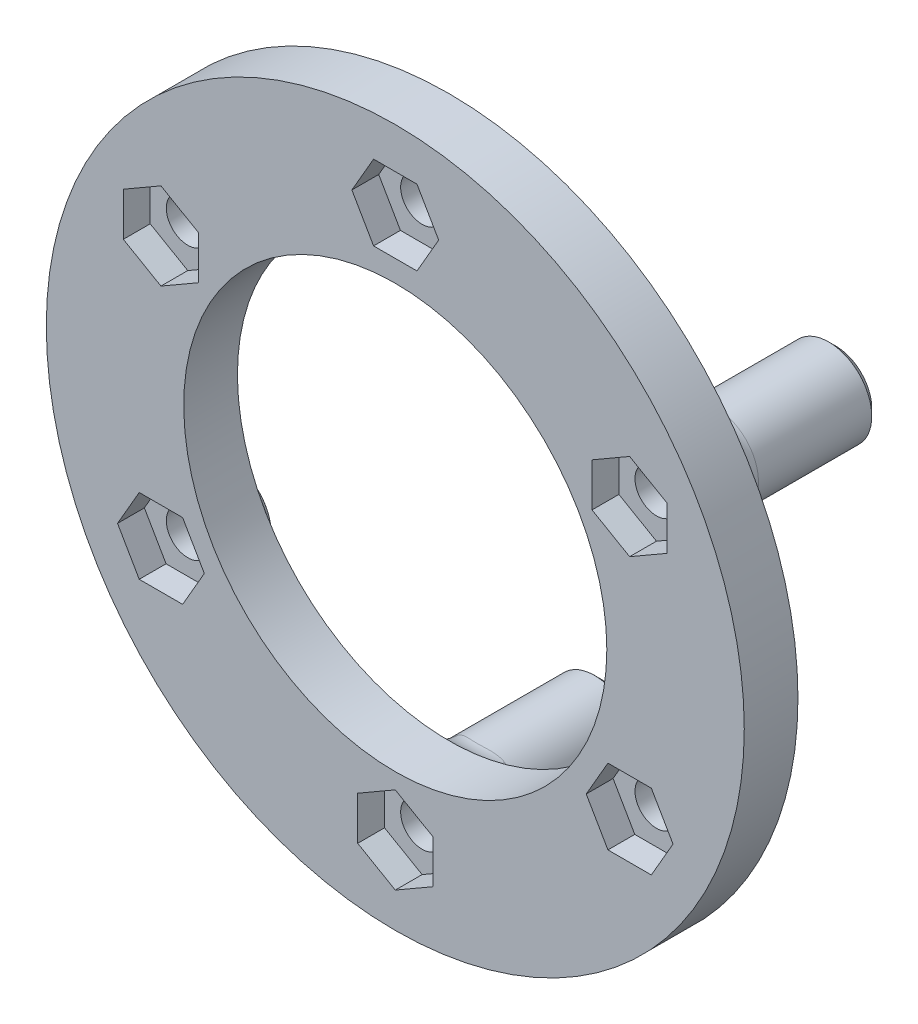
SolidWorks part; units mm, degrees
material "ABS"
ref_plane "Front Plane" through (0, 0, 0) normal (0, 0, 1) x (1, 0, 0)
ref_plane "Top Plane" through (0, 0, 0) normal (0, 1, 0) x (1, 0, 0)
ref_plane "Right Plane" through (0, 0, 0) normal (1, 0, 0) x (0, 0, -1)
sketch "Sketch2" plane through (0, 0, 0) normal (0, 0, 1) x (1, 0, 0)
  line L0 (0, 25.2) -> (0, 0) construction
  line L1 (0, 0) -> (24.6817, 14.25) construction
  circle A0 centre (0, 0) radius 32.5
  circle A1 centre (0, 0) radius 19.7
  circle A2 centre (0, 0) radius 25.2 construction
  circle A3 centre (0, 25.2) radius 2
  circle A4 centre (0, 0) radius 28.5 construction
  circle A5 centre (21.8238, 12.6) radius 2
  circle A11 centre (0, 0) radius 5.4 construction
  circle A14 centre (0, 25.2) radius 4 construction
  circle A15 centre (0, 0) radius 21.2 construction
  circle A20 centre (21.8238, -12.6) radius 2
  circle A21 centre (0, -25.2) radius 2
  circle A22 centre (-21.8238, -12.6) radius 2
  circle A23 centre (-21.8238, 12.6) radius 2
  point P17 (0, 0)
  point P24 (0, 0)
  dimension "D1" = 65
  dimension "D2" = 50.4
  dimension "D4" = 4
  dimension "D3" = 10.8
  dimension "D10" = 8
  dimension "D5" = 4
  dimension "D9" = 1.5
  dimension "D11" = 60
  dimension "D6" = 6
extrude "Boss-Extrude1" add sketch "Sketch2" along normal blind 5
sketch "Sketch3" plane through (0, 0, 5) normal (0, 0, 1) x (1, 0, 0)
  line L0 (0, 25.2) -> (0, 0) construction
  line L13 (-4.0415, 25.2) -> (-2.0207, 21.7)
  line L14 (-2.0207, 21.7) -> (2.0207, 21.7)
  line L15 (2.0207, 21.7) -> (4.0415, 25.2)
  line L16 (4.0415, 25.2) -> (2.0207, 28.7)
  line L17 (2.0207, 28.7) -> (-2.0207, 28.7)
  line L18 (-2.0207, 28.7) -> (-4.0415, 25.2)
  line L20 (21.8238, 8.5585) -> (25.3238, 10.5793)
  line L21 (25.3238, 10.5793) -> (25.3238, 14.6207)
  line L22 (25.3238, 14.6207) -> (21.8238, 16.6415)
  line L23 (21.8238, 16.6415) -> (18.3238, 14.6207)
  line L24 (18.3238, 14.6207) -> (18.3238, 10.5793)
  line L25 (18.3238, 10.5793) -> (21.8238, 8.5585)
  circle A0 centre (0, 25.2) radius 3.5 construction
  circle A1 centre (21.8238, 12.6) radius 3.5 construction
  dimension "D1" = 7
  dimension "D2" = 7
extrude "Cut-Extrude1" cut sketch "Sketch3" against normal blind 2.5
pattern_circular "CirPattern1" count 3 over 360 about axis through (0, 0, 0) along (0, 0, 1) of "Cut-Extrude1"
sketch "Sketch4" plane through (0, 0, 0) normal (0, 0, -1) x (-1, 0, 0)
  circle A0 centre (0, 25.2) radius 3
  circle A1 centre (0, 25.2) radius 4
  dimension "D1" = 6
extrude "Boss-Extrude2" add sketch "Sketch4" along normal blind 1.5
fillet "Fillet1" radius 1.5 1 edges at (4, 25.2, 0)
fillet "Fillet2" radius 0.5 1 edges at (-4, 25.2, -1.5)
chamfer "Chamfer1" distance 0.25 angle 45 1 edges at (-3, 25.2, -1.5)
pattern_circular "CirPattern2" count 3 over 360 about axis through (0, 0, 0) along (0, 0, 1) of "Boss-Extrude2", "Fillet1", "Fillet2", "Chamfer1"
sketch "Sketch5" plane through (0, 0, 0) normal (0, 0, -1) x (-1, 0, 0)
  circle A0 centre (21.8238, 12.6) radius 4
  circle A1 centre (0, -25.2) radius 4
  circle A2 centre (-21.8238, 12.6) radius 4
  circle M8 centre (-21.8238, 12.6) radius 2
  circle M9 centre (0, -25.2) radius 2
  circle M10 centre (21.8238, 12.6) radius 2
  dimension "D1" = 8
  dimension "D2" = 8
  dimension "D3" = 8
extrude "Boss-Extrude3" add sketch "Sketch5" along normal blind 14.2 contours A2 M8 | A0 M10 | A1 M9
fillet "Fillet3" radius 3 3 edges at (-17.8238, 12.6, 0) (4, -25.2, 0) (25.8238, 12.6, 0)
chamfer "Chamfer2" distance 0.65 angle 45 3 edges at (-25.8238, 12.6, -14.2) (-4, -25.2, -14.2) (17.8238, 12.6, -14.2)
equation "\"Nr\"= 117"
equation "\"module\"= 0.6"
equation "\"pressure_angle\"= 20.0"
equation "\"h_a\"= 0.6"
equation "\"h_f\"= 0.75"
equation "\"clr_tip_root\"= 0.15000000000000002"
equation "\"dp_r\"= 70.2"
equation "\"db_r\"= 65.96642197917078"
equation "\"fw_r\"= 8.20766970174645"
equation "\"alpha_r\"= 0.8539582918412272"
equation "\"beta_r\"= 3.2463781221439927"
equation "\"bearing_ID\"= 65"
equation "\"bearing_OD\"= 85"
equation "\"bearing_height\"= 10"
equation "\"clearance_planet\"= 1.5"
equation "\"case_dist\"= 19.182493784294785"
equation "\"Motor_case_OD_max\"= 114.5"
equation "\"case_mounting_PCD\"= 107.0"
equation "\"bearing mount thickness\"= IIF((\"bearing_OD\" + \"output_mounting_hole_dia\" * 4) > (\"Nr\" * \"module\" + 2 * \"h_b\"), \"output_mounting_hole_dia\" * 2, ((\"Nr\" * \"module\" + 2 * \"h_b\" - (\"bearing_OD\" + \"output_mounting_hole_dia\" * 4)) / 2) + \"output_mounting_hole_dia\" * 2 + \"standard_clearance_1_5mm\")"
equation "\"case_mounting_hole_dia\"= 3"
equation "\"output_mounting_PCD\"= 93"
equation "\"output_mounting_hole_dia\"= 4"
equation "\"clearance_case_mount_holes_shell_thickness\"= 1"
equation "\"motor_case_OD_base\"= 105.0"
equation "\"sec_carrier_thickness\"= 5"
equation "\"sun_coupler_hub_thickness\"= 4"
equation "\"clearance_sun_coupler_sec_carrier\"= 1.5"
equation "\"clearance_motor_and_case\"= 14.0"
equation "\"motor_OD\"= 72"
equation "\"Motor_case_thickness\"= 2.5"
equation "\"Motor_case_ID\"= 100.0"
equation "\"case_mounting_hole_shift\"= 1.0"
equation "\"output_mounting_nut_wrench_size\"= 7"
equation "\"output_mounting_nut_thickness\"= 3.2"
equation "\"case_mounting_hole_allen_socket_dia\"= 5.5"
equation "\"output_mounting_nut_depth\"= 3"
equation "\"case_mounting_bolt_depth\"= 4.5"
equation "\"Ns\"= 18"
equation "\"Np_b\"= 66"
equation "\"ring_radial_thickness\"= 8.899999999999999"
equation "\"ring_OD\"= 88.0"
equation "\"ring_to_chamfer_clearance\"= 0.5"
equation "\"Motor_case_OD_base_to_chamfer\"= 5"
equation "\"pattern_offset_from_motor_case_OD_base\"= 3"
equation "\"pattern_bulge_dia\"= 3"
equation "\"pattern_num_bulge\"= 18"
equation "\"pattern_depth\"= 2"
equation "\"motor_height\"= 27"
equation "\"case_mounting_wrench_size\"= 5.5"
equation "\"case_mounting_nut_clearance\"= 2"
equation "\"base_plate_thickness\"= 4"
equation "\"case_mounting_nut_thickness\"= 2.4"
equation "\"case_mounting_surface_height\"= 4"
equation "\"motor_mount_hole_PCD\"= 32"
equation "\"motor_mount_hole_dia\"= 4"
equation "\"motor_mount_hole_num\"= 4"
equation "\"central_hole_offset_from_motor_mount_PCD\"= 5"
equation "\"wire_slot_dist_from_center\"= 26"
equation "\"wire_slot_length\"= 10"
equation "\"wire_slot_radius\"= 2.5"
equation "\"driver_upper_holes_dist_from_center\"= 29"
equation "\"driver_lower_holes_dist_from_center\"= 13"
equation "\"driver_side_holes_dist_from_center\"= 22.5"
equation "\"driver_mount_holes_dia\"= 3"
equation "\"driver_mount_inserts_OD\"= 4.8"
equation "\"driver_mount_thickness\"= 1.5"
equation "\"driver_mount_height\"= 6"
equation "\"air_flow_hole_offset\"= 3"
equation "\"num_planet\"= 3"
equation "\"planet_pin_bolt_dia\"= 5"
equation "\"planet_pin_socket_head_dia\"= 8.5"
equation "\"carrier_PCD\"= 50.4"
equation "\"D1@Sketch2\"=\"bearing_ID\""
equation "\"D2@Sketch2\"=\"carrier_PCD\""
equation "\"D6@Sketch2\"=\"num_planet\"*2"
equation "\"D1@CirPattern1\"=\"num_planet\""
equation "\"planet_shaft_dia\"= 8"
equation "\"planet_shaft_step_offset\"= 1"
equation "\"carrier_trapezoidal_support_sun_offset\"= 5"
equation "\"carrier_trapezoidal_support_hole_PCD_offset_bearing_ID\"= 4"
equation "\"carrier_trapezoidal_support_hole_dia\"= 3"
equation "\"carrier_trapezoidal_support_hole_socket_head_dia\"= 5.5"
equation "\"carrier_bearing_step_width\"= 1.5"
equation "\"standard_clearance_1_5mm\"= 1.5"
equation "\"standard_fillet_1_5mm\"= 1.5"
equation "\"sun_shaft_bearing_OD\"= 16"
equation "\"sun_shaft_bearing_width\"= 5"
equation "\"standard_bearing_insertion_chamfer\"= 0.5"
equation "\"D5@Sketch2\"=\"carrier_trapezoidal_support_hole_PCD_offset_bearing_ID\""
equation "\"D3@Sketch2\"=\"Ns\"*\"module\""
equation "\"carrier_trapezoidal_support_hole_wrench_size\"= 5.5"
equation "\"planet_pin_bolt_wrench_size\"= 8"
equation "\"D1@Boss-Extrude1\"=\"sec_carrier_thickness\""
equation "\"D1@Cut-Extrude1\"=\"sec_carrier_thickness\"/2"
equation "\"D2@Sketch4\"=\"planet_shaft_step_offset\""
equation "\"D1@Boss-Extrude2\"=\"clearance_planet\""
equation "\"D1@Fillet1\"=\"standard_fillet_1_5mm\""
equation "\"D1@Chamfer1\"=\"standard_bearing_insertion_chamfer\"/2"
equation "\"D1@Fillet2\"=\"standard_fillet_1_5mm\"/3"
equation "\"D1@CirPattern2\"=\"num_planet\""
equation "\"D10@Sketch2\"=6+\"planet_shaft_step_offset\"*2"
equation "\"D9@Sketch2\"=\"standard_clearance_1_5mm\""
equation "\"D1@Sketch3\"=7"
equation "\"D11@Sketch2\"=180/\"num_planet\""
equation "\"D2@Sketch3\"=7"
equation "\"pressure angle\"= 20.0"
equation "\"h_b\"= 0.75"
equation "\"dp_s\"= 10.799999999999999"
equation "\"db_s\"= 10.14868030448781"
equation "\"fw_s_calc\"= 11.182493784294786"
equation "\"alpha_s\"= 0.8539582918412414"
equation "\"beta_s\"= 8.292083416317517"
equation "\"dp_p_b\"= 39.6"
equation "\"db_p_b\"= 37.211827783121976"
equation "\"fw_p_s\"= 9.70766970174645"
equation "\"alpha_p_b\"= 0.8539582918412414"
equation "\"beta_p_b\"= 1.0193561435902443"
equation "\"planet_bearing_OD\"= 12"
equation "\"planet_bearing_width\"= 3.5"
equation "\"planet_bore\"= 10"
equation "\"motor_output_hole_PCD\"= 22"
equation "\"motor_output_hole_dia\"= 3"
equation "\"motor_output_hole_num\"= 4"
equation "\"sun_shaft_bearing_ID\"= 8"
equation "\"sun_hub_dia\"= 31.0"
equation "\"sun_central_bolt_dia\"= 5"
equation "\"sun_central_bolt_socket_head_dia\"= 8.5"
equation "\"fw_s_used\"= 28.89016348604124"
equation "\"motor_output_hole_CSK_OD\"= 6"
equation "\"motor_output_hole_CSK_head_height\"= 1.5"
equation "\"bearing_retainer_thickness\"= 2"
equation "\"Np_s\"= 33"
equation "\"fw_p_b\"= 11.182493784294786"
equation "\"dp_p_s\"= 19.8"
equation "\"db_p_s\"= 18.605913891560988"
equation "\"alpha_p_s\"= 0.8539582918412414"
equation "\"beta_p_s\"= 3.7466288708629714"
